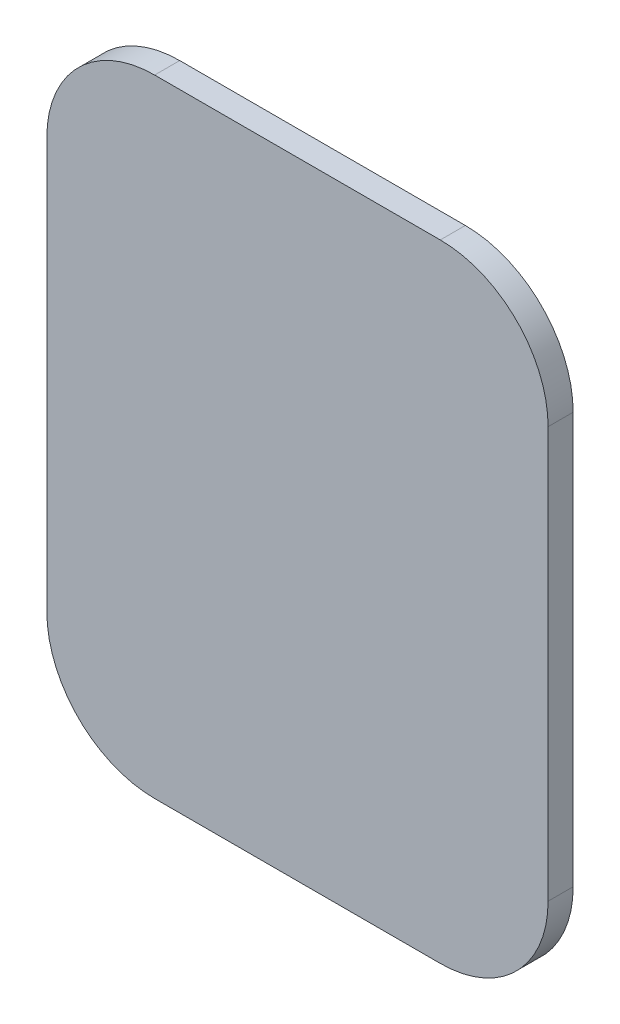
SolidWorks part; units mm, degrees
ref_plane "mating-plane" through (0, 0, 0) normal (0, 0, 1) x (1, 0, 0)
ref_plane "Top Plane" through (0, 0, 0) normal (0, 1, 0) x (1, 0, 0)
ref_plane "Right Plane" through (0, 0, 0) normal (1, 0, 0) x (0, 0, -1)
ref_axis "axis" through (0, 0, -0.4622) along (0, 0, 1)
sketch "Sketch9" plane through (0, 0, 0) normal (0, 0, 1) x (1, 0, 0)
  line L0 (1, 0) -> (-1, 0) construction
  line L2 (0, 1.25) -> (0, -1.25) construction
  line L20 (1, 0.8198) -> (1, -0.8198)
  line L21 (0.5698, -1.25) -> (-0.5698, -1.25)
  line L22 (1, -0.8198) -> (0.5698, -0.8198) construction
  line L23 (0.5698, -0.8198) -> (0.5698, -1.25) construction
  line L24 (1, -0.8198) -> (1, -1.25) construction
  line L25 (1, -1.25) -> (0.5698, -1.25) construction
  line L26 (-1, -0.8198) -> (-1, 0.8198)
  line L27 (1, -1.25) -> (-1, -1.25) construction
  line L28 (1, -1.25) -> (1, 1.25) construction
  line L29 (1, 1.25) -> (-1, 1.25) construction
  line L30 (-1, -1.25) -> (-1, 1.25) construction
  line L31 (-0.5698, 1.25) -> (0.5698, 1.25)
  arc A1 (1, -0.8198) -> (0.5698, -1.25) centre (0.5698, -0.8198) cw
  arc A2 (-0.5698, -1.25) -> (-1, -0.8198) centre (-0.5698, -0.8198) cw
  arc A3 (-1, 0.8198) -> (-0.5698, 1.25) centre (-0.5698, 0.8198) cw
  arc A4 (0.5698, 1.25) -> (1, 0.8198) centre (0.5698, 0.8198) cw
extrude "landing-pad-2.5x2" add sketch "Sketch9" against normal blind 0.1 separate body
sketch "Sketch18" plane through (0, 0, 0) normal (0, 0, 1) x (1, 0, 0)
  line L0 (1, 0) -> (-1, 0) construction
  line L2 (0, 1) -> (0, -1) construction
  line L20 (1, 0.5698) -> (1, -0.5698)
  line L21 (0.5698, -1) -> (-0.5698, -1)
  line L22 (1, -0.5698) -> (0.5698, -0.5698) construction
  line L23 (0.5698, -0.5698) -> (0.5698, -1) construction
  line L24 (1, -0.5698) -> (1, -1) construction
  line L25 (1, -1) -> (0.5698, -1) construction
  line L26 (-1, -0.5698) -> (-1, 0.5698)
  line L27 (1, -1) -> (-1, -1) construction
  line L28 (1, -1) -> (1, 1) construction
  line L29 (1, 1) -> (-1, 1) construction
  line L30 (-1, -1) -> (-1, 1) construction
  line L31 (-0.5698, 1) -> (0.5698, 1)
  arc A1 (1, -0.5698) -> (0.5698, -1) centre (0.5698, -0.5698) cw
  arc A2 (-0.5698, -1) -> (-1, -0.5698) centre (-0.5698, -0.5698) cw
  arc A3 (-1, 0.5698) -> (-0.5698, 1) centre (-0.5698, 0.5698) cw
  arc A4 (0.5698, 1) -> (1, 0.5698) centre (0.5698, 0.5698) cw
extrude "landing-pad-2x2" [suppressed] add sketch "Sketch18" against normal blind 0.1 separate body
sketch "Sketch3" plane through (0, 0, 0) normal (0, 0, -1) x (-1, 0, 0)
  circle A0 centre (0, 0) radius 0.535
extrude "pin-body" [suppressed] add sketch "Sketch3" against normal blind 2.93 separate body
sketch "Sketch11" plane through (0, 0, 0) normal (0, 1, 0) x (1, 0, 0)
  line L0 (-0.005, 0) -> (-0.535, 0)
  line L2 (-0.535, 0) -> (-0.535, -0.53)
  arc A0 (-0.005, 0) -> (-0.535, -0.53) centre (-0.005, -0.53) ccw
revolve "dome" [suppressed] cut sketch "Sketch11" angle 360 about axis through (0, 0, -0.4622) along (0, 0, 1)
sketch "Sketch17" [suppressed] plane through (0, 0, 0) normal (0, 0, 1) x (1, 0, 0)
  line L1 (-7.7123, 1.2258) -> (6.7302, 1.2258)
  line L2 (-7.7123, 1.2258) -> (-7.7123, -1.8908)
  line L3 (-7.7123, -1.8908) -> (6.7302, -1.8908)
  line L4 (6.7302, 1.2258) -> (6.7302, -1.8908)
extrude "fake-thing" [suppressed] add sketch "Sketch17" along normal blind 0.7 separate body
sketch "Sketch8" [suppressed] plane through (0, 0, 0) normal (0, 0, -1) x (-1, 0, 0)
  circle A0 centre (0, 0) radius 0.749
  circle A1 centre (0, 0) radius 0.535
extrude "body-front" [suppressed] add sketch "Sketch8" against normal blind 3.81 from surface separate body starting at face at (0, 0, -0.1)
sketch "Sketch15" [suppressed] plane through (0, 0, 4.51) normal (0, 0, 1) x (1, 0, 0)
  circle A0 centre (0, 0) radius 0.535
extrude "plug" [suppressed] add sketch "Sketch15" against normal blind 0.75
sketch "Sketch13" [suppressed] plane through (0, 0, 4.51) normal (0, 0, 1) x (1, 0, 0)
  circle A1 centre (0, 0) radius 0.89
  circle A2 centre (0, 0) radius 0.749
extrude "body-back" [suppressed] add sketch "Sketch13" against normal blind 2
sketch "Sketch14" [suppressed] plane through (0, 0, 2.51) normal (0, 0, -1) x (-1, 0, 0)
  circle A0 centre (0, 0) radius 1.08
extrude "flange" [suppressed] add sketch "Sketch14" along normal blind 0.25
ref_plane "PCB-edge" [suppressed] through (0, 0, 2.51) normal (0, 0, 1) x (1, 0, 0)
sketch "Sketch16" [suppressed] plane through (0, 0, 0) normal (1, 0, 0) x (0, 0, -1)
  line L5 (-2.26, -1.08) -> (-2.26, 1.08) construction
  line L6 (-2.26, -0.749) -> (-2.45, -0.749) construction
  line L7 (-2.45, -0.749) -> (-2.1, -0.749)
  line L8 (-2.45, -0.749) -> (-2.45, -0.814)
  line L9 (-2.45, -0.814) -> (-2.1, -0.749)
revolve "rib" [suppressed] add sketch "Sketch16" angle 360 about axis through (0, 0, -0.4622) along (0, 0, 1)
